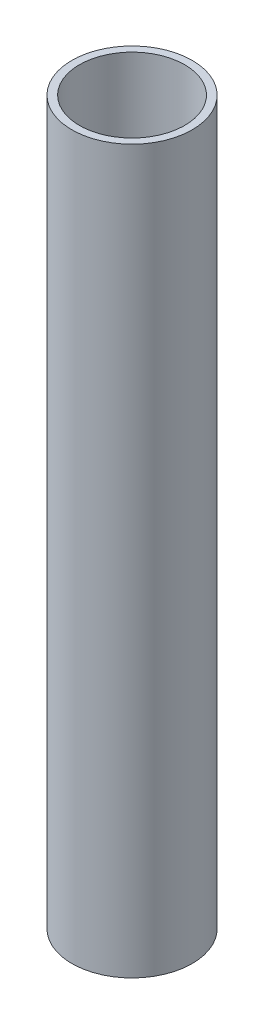
SolidWorks part; units mm, degrees
material "6061-T6 (SS)"
ref_plane "Front Plane" through (0, 0, 0) normal (0, 0, 1) x (1, 0, 0)
ref_plane "Top Plane" through (0, 0, 0) normal (0, 1, 0) x (1, 0, 0)
ref_plane "Right Plane" through (0, 0, 0) normal (1, 0, 0) x (0, 0, -1)
sketch "Sketch1" plane through (0, 0, 0) normal (0, 1, 0) x (1, 0, 0)
  circle A0 centre (0, 0) radius 25.4
  circle A1 centre (0, 0) radius 22.225
  dimension "D1" = 50.8
  dimension "D2" = 3.175
extrude "Boss-Extrude1" add sketch "Sketch1" along normal blind 304.8
equation "\"TubeThick\"=0.125"
equation "\"D2@Sketch1\"=\"TubeThick\""
equation "\"Length\"=12"
equation "\"TubeLen\"=12"
